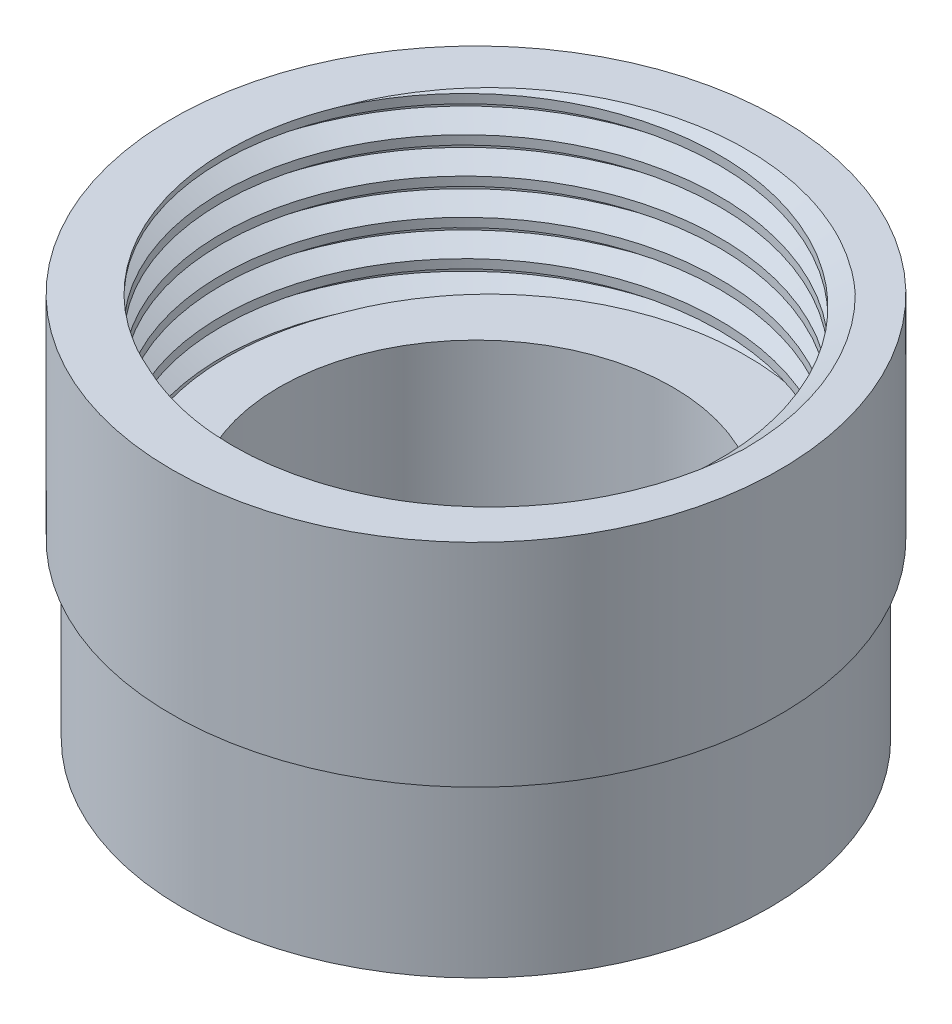
SolidWorks part; units mm, degrees
ref_plane "Front Plane" through (0, 0, 0) normal (0, 0, 1) x (1, 0, 0)
ref_plane "Top Plane" through (0, 0, 0) normal (0, 1, 0) x (1, 0, 0)
ref_plane "Right Plane" through (0, 0, 0) normal (1, 0, 0) x (0, 0, -1)
sketch "Sketch1" plane through (0, 0, 0) normal (0, 1, 0) x (1, 0, 0)
  circle A0 centre (0, 0) radius 11
  circle A1 centre (0, 0) radius 16.4
  dimension "D1" = 22
  dimension "D2" = 32.8
extrude "Boss-Extrude1" add sketch "Sketch1" along normal blind 11.5217
sketch "Sketch2" plane through (0, 11.5217, 0) normal (0, 1, 0) x (1, 0, 0)
  circle A1 centre (0, 0) radius 15
  circle A2 centre (0, 0) radius 17
  dimension "D1" = 34
  dimension "D3" = 30
extrude "Boss-Extrude2" add sketch "Sketch2" along normal blind 10
sketch "Sketch3" plane through (0, 11.5217, 0) normal (0, -1, 0) x (1, 0, 0)
  circle A0 centre (0, 0) radius 16.4
  circle A1 centre (0, 0) radius 17
  dimension "D1" = 34
  dimension "D2" = 32.8
extrude "Boss-Extrude3" add sketch "Sketch3" along normal blind 1.86
thread "Thread3" pitch 2 start angle 0, offset 2, length 20, pitch 2, diameter 30
ref_plane "Plane2" through (15, 9.5217, 0) normal (0, 0, 1) x (1, 0, 0)
sketch "Thread Profile2" plane through (15, 9.5217, 0) normal (0, 0, 1) x (1, 0, 0)
  line L0 (0, 0) -> (0, 2) construction
  line L11 (0, 0) -> (0, 1.75)
  line L12 (0, 1.75) -> (-1.0825, 1.125)
  line L13 (-1.0825, 1.125) -> (-1.0825, 0.625)
  line L15 (-1.0825, 0.625) -> (0, 0)
  line L17 (-1.0825, 0.875) -> (0, 0.875) construction
  point P2 (0, 0)
  dimension "Pitch" = 2
  dimension "Profile_Angle" = 60
  dimension "Profile_Land" = 0.5
  dimension "Profile_Height" = 1.0825
equation "\"clearance\"= 0.3mm ' Freely and easily sliding. Used as a gap between the telescopic sections."
equation "\"clearance2\" = 0.1mm ' Used as a gap between rings next to each other."
equation "\"interference\"= 0.1mm ' This is like clearance1 but when two parts should just fit together rather than freely spin."
equation "\"D1@Sketch2\"=34.00mm"
equation "\"D2@Sketch1\"=33.00mm - \"interference\" * 2"
equation "\"clearance1\" = 0.3mm ' Sliding but a little resistance. Used as a gap between the core and the rotating rings."
equation "\"pegLength\"= 1.5mm ' The length of the pegs that stick out from the telescopic sections."
equation "\"D2@Sketch3\"=33.00mm - \"interference\" * 2"
